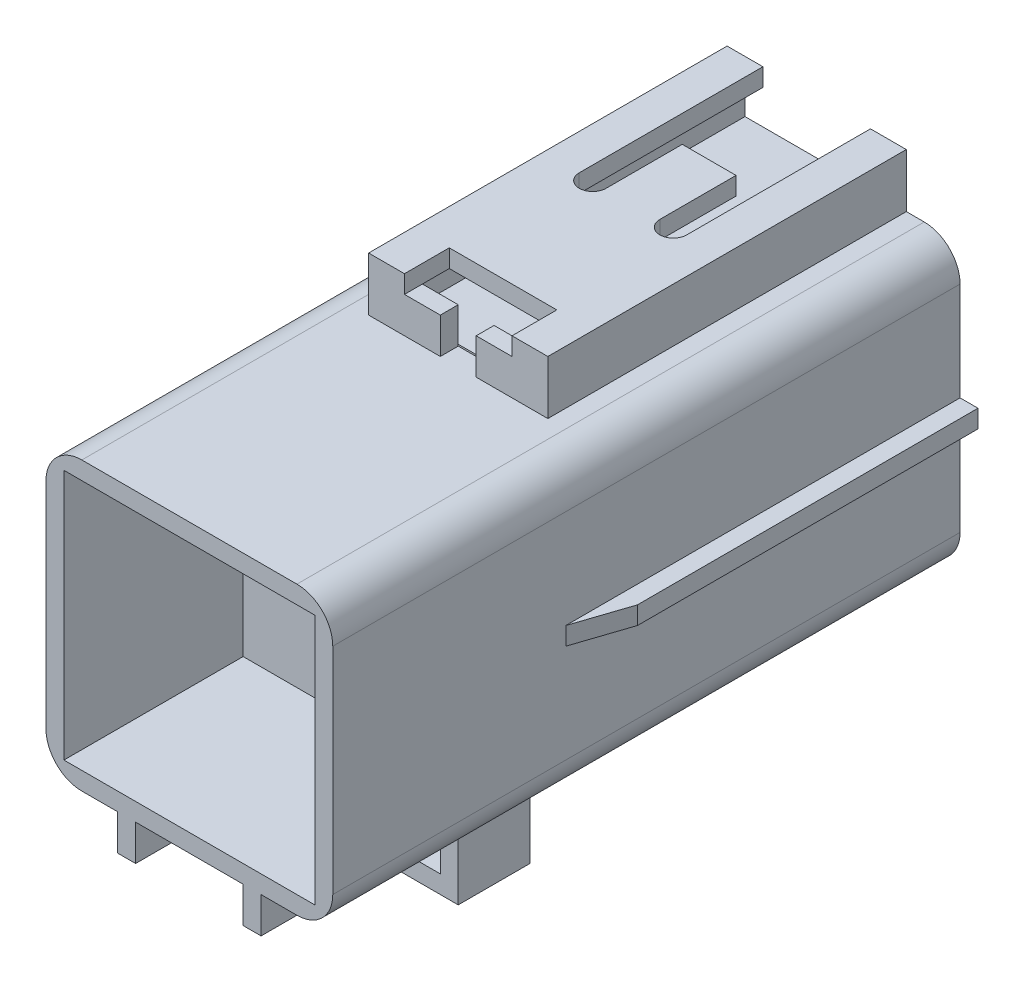
SolidWorks part; units mm, degrees
ref_plane "正面" through (0, 0, 0) normal (0, 0, 1) x (1, 0, 0)
ref_plane "平面" through (0, 0, 0) normal (0, 1, 0) x (1, 0, 0)
ref_plane "右側面" through (0, 0, 0) normal (1, 0, 0) x (0, 0, -1)
sketch "ｽｹｯﾁ1" plane through (0, 0, 0) normal (0, 0, 1) x (1, 0, 0)
  line L1 (8, -8) -> (-8, -8)
  line L2 (8, -8) -> (8, 8)
  line L3 (8, 8) -> (-8, 8)
  line L4 (-8, -8) -> (-8, 8)
  line L5 (8, -8) -> (-8, 8) construction
  line L6 (8, 8) -> (-8, -8) construction
  point P0 (0, 0)
  dimension "D1" = 16
extrude "ﾎﾞｽ - 押し出し1" add sketch "ｽｹｯﾁ1" along normal blind 35
fillet "ﾌｨﾚｯﾄ1" radius 2 4 edges at (8, -8, 17.5) (-8, -8, 17.5) (-8, 8, 17.5) (8, 8, 17.5)
sketch "ｽｹｯﾁ2" plane through (0, -8, 0) normal (0, -1, 0) x (1, 0, 0)
  line L0 (0, 35) -> (0, 0) construction
  line L1 (-6, 35) -> (6, 35) construction
  line L3 (-4, 35) -> (4, 35)
  line L4 (-4, 35) -> (-4, 20)
  line L5 (-4, 20) -> (4, 20)
  line L6 (4, 35) -> (4, 20)
  point P9 (0, 0)
  dimension "D1" = 8
  dimension "D2" = 15
extrude "ﾎﾞｽ - 押し出し2" add sketch "ｽｹｯﾁ2" along normal blind 6
sketch "ｽｹｯﾁ3" plane through (0, 0, 35) normal (0, 0, 1) x (1, 0, 0)
  line L0 (4, -14) -> (-4, -14) construction
  line L1 (-3, -8) -> (3, -8)
  line L2 (-3, -8) -> (-3, -13)
  line L3 (-3, -13) -> (3, -13)
  line L4 (3, -8) -> (3, -13)
  line L5 (-4, -14) -> (-4, -8) construction
  line L6 (4, -14) -> (4, -8) construction
  line L7 (-6, -8) -> (-4, -8) construction
  dimension "D1" = 1
  dimension "D2" = 1
  dimension "D3" = 1
extrude "ｶｯﾄ - 押し出し2" cut sketch "ｽｹｯﾁ3" against normal up to next
sketch "ｽｹｯﾁ7" plane through (0, 0, 35) normal (0, 0, 1) x (1, 0, 0)
  line L0 (-4, -10) -> (-4, -14)
  line L1 (-4, -14) -> (-4, -8) construction
  line L2 (-4, -14) -> (4, -14)
  line L3 (4, -14) -> (4, -10)
  line L4 (4, -14) -> (4, -8) construction
  line L5 (4, -10) -> (-4, -10)
  dimension "D1" = 4
extrude "ｶｯﾄ - 押し出し4" cut sketch "ｽｹｯﾁ7" against normal blind 11
sketch "ｽｹｯﾁ8" plane through (0, 8, 0) normal (0, 1, 0) x (1, 0, 0)
  line L0 (0, -35) -> (0, 0) construction
  line L1 (6, -35) -> (-6, -35) construction
  line L2 (6, 0) -> (-6, 0) construction
  line L4 (5, 0) -> (-5, 0)
  line L5 (5, 0) -> (5, -20)
  line L6 (5, -20) -> (-5, -20)
  line L7 (-5, 0) -> (-5, -20)
  dimension "D1" = 10
  dimension "D2" = 20
extrude "ﾎﾞｽ - 押し出し3" add sketch "ｽｹｯﾁ8" along normal blind 3
sketch "ｽｹｯﾁ9" plane through (0, 11, 0) normal (0, 1, 0) x (1, 0, 0)
  line L0 (3, 0) -> (3, -11)
  line L1 (5, 0) -> (-5, 0) construction
  line L2 (3, -11) -> (1.5, -11)
  line L3 (1.5, -11) -> (1.5, -6)
  line L4 (0, 0) -> (0, -20) construction
  line L5 (-5, -20) -> (5, -20) construction
  line L6 (1.5, -6) -> (-1.5, -6)
  line L7 (-1.5, -11) -> (-1.5, -6)
  line L8 (-3, -11) -> (-1.5, -11)
  line L9 (-3, 0) -> (-3, -11)
  line L10 (3, 0) -> (-3, 0)
  line L12 (3, -20) -> (-3, -20)
  line L13 (3, -20) -> (3, -17.5)
  line L14 (3, -17.5) -> (-3, -17.5)
  line L15 (-3, -20) -> (-3, -17.5)
  point P10 (1.5, -8.5)
  point P13 (0, -6)
  dimension "D1" = 11
  dimension "D2" = 1.5
  dimension "D3" = 1.5
  dimension "D4" = 6
  dimension "D5" = 2.5
  dimension "D6" = 6
extrude "ｶｯﾄ - 押し出し5" cut sketch "ｽｹｯﾁ9" against normal blind 1
fillet "ﾌｨﾚｯﾄ2" radius 0.75 4 edges at (-3, 10.5, 11) (-1.5, 10.5, 11) (1.5, 10.5, 11) (3, 10.5, 11)
sketch "ｽｹｯﾁ10" plane through (0, 0, 0) normal (0, 0, -1) x (-1, 0, 0)
  line L0 (0, 10) -> (0, -8) construction
  line L1 (-3, 10) -> (3, 10) construction
  line L2 (6, -8) -> (-6, -8) construction
  line L3 (-8, 0) -> (8, 0) construction
  line L4 (-8, -6) -> (-8, 6) construction
  line L5 (8, 6) -> (8, -6) construction
  circle A0 centre (-3.1, 3.1) radius 2.5
  circle A1 centre (3.1, 3.1) radius 2.5
  circle A2 centre (3.1, -3.1) radius 2.5
  circle A3 centre (-3.1, -3.1) radius 2.5
  dimension "D1" = 5
  dimension "D2" = 3.1
  dimension "D3" = 3.1
extrude "ｶｯﾄ - 押し出し6" cut sketch "ｽｹｯﾁ10" against normal blind 10
sketch "ｽｹｯﾁ11" plane through (0, 0, 35) normal (0, 0, 1) x (1, 0, 0)
  line L0 (6, 8) -> (-6, 8) construction
  line L1 (7, -7) -> (-7, -7)
  line L2 (7, -7) -> (7, 7)
  line L3 (7, 7) -> (-7, 7)
  line L4 (-7, -7) -> (-7, 7)
  line L5 (7, -7) -> (-7, 7) construction
  line L6 (7, 7) -> (-7, -7) construction
  point P0 (0, 0)
  dimension "D1" = 1
extrude "ｶｯﾄ - 押し出し7" cut sketch "ｽｹｯﾁ11" against normal blind 10
sketch "ｽｹｯﾁ12" plane through (0, 0, 0) normal (0, 0, -1) x (-1, 0, 0)
  line L0 (-5, 11) -> (-3, 11) construction
  line L1 (-4, 10) -> (4, 10)
  line L2 (-4, 10) -> (-4, 8.0917)
  line L3 (-4, 8.0917) -> (4, 8.0917)
  line L4 (4, 10) -> (4, 8.0917)
  line L5 (-5, 11) -> (-5, 8) construction
  line L6 (5, 11) -> (5, 8) construction
  dimension "D1" = 1
  dimension "D2" = 1
  dimension "D3" = 1
extrude "ｶｯﾄ - 押し出し8" cut sketch "ｽｹｯﾁ12" against normal blind 19
sketch "ｽｹｯﾁ13" plane through (0, 10, 0) normal (0, 1, 0) x (1, 0, 0)
  line L0 (0, -20) -> (0, -19) construction
  line L1 (-3, -20) -> (3, -20) construction
  line L2 (-3, -19) -> (3, -19) construction
  line L4 (1, -20) -> (-1, -20)
  line L5 (1, -20) -> (1, -19)
  line L6 (1, -19) -> (-1, -19)
  line L7 (-1, -20) -> (-1, -19)
  dimension "D1" = 1
extrude "ｶｯﾄ - 押し出し9" cut sketch "ｽｹｯﾁ13" against normal blind 2
sketch "ｽｹｯﾁ14" plane through (8, 0, 0) normal (1, 0, 0) x (0, 0, -1)
  line L0 (-35, 0) -> (0, 0) construction
  line L1 (-35, -6) -> (-35, 6) construction
  line L2 (0, -6) -> (0, 6) construction
  line L4 (0, 0.5) -> (-22, 0.5)
  line L5 (0, 0.5) -> (0, -0.5)
  line L6 (0, -0.5) -> (-22, -0.5)
  line L7 (-22, 0.5) -> (-22, -0.5)
  dimension "D1" = 1
  dimension "D2" = 22
extrude "ﾎﾞｽ - 押し出し4" add sketch "ｽｹｯﾁ14" along normal blind 1
sketch "ｽｹｯﾁ16" plane through (0, 0.5, 0) normal (0, 1, 0) x (1, 0, 0)
  line L0 (8, -22) -> (9, -22)
  line L1 (9, -22) -> (9, -19)
  line L2 (9, 0) -> (9, -22) construction
  line L3 (9, -19) -> (8, -22)
  dimension "D1" = 3
extrude "ｶｯﾄ - 押し出し10" cut sketch "ｽｹｯﾁ16" against normal blind 1
mirror "ﾐﾗｰ1" about plane through (0, 0, 0) normal (1, 0, 0) of "ﾎﾞｽ - 押し出し4"
mirror "ﾐﾗｰ2" about plane through (0, 0, 0) normal (1, 0, 0) of "ｶｯﾄ - 押し出し10"
